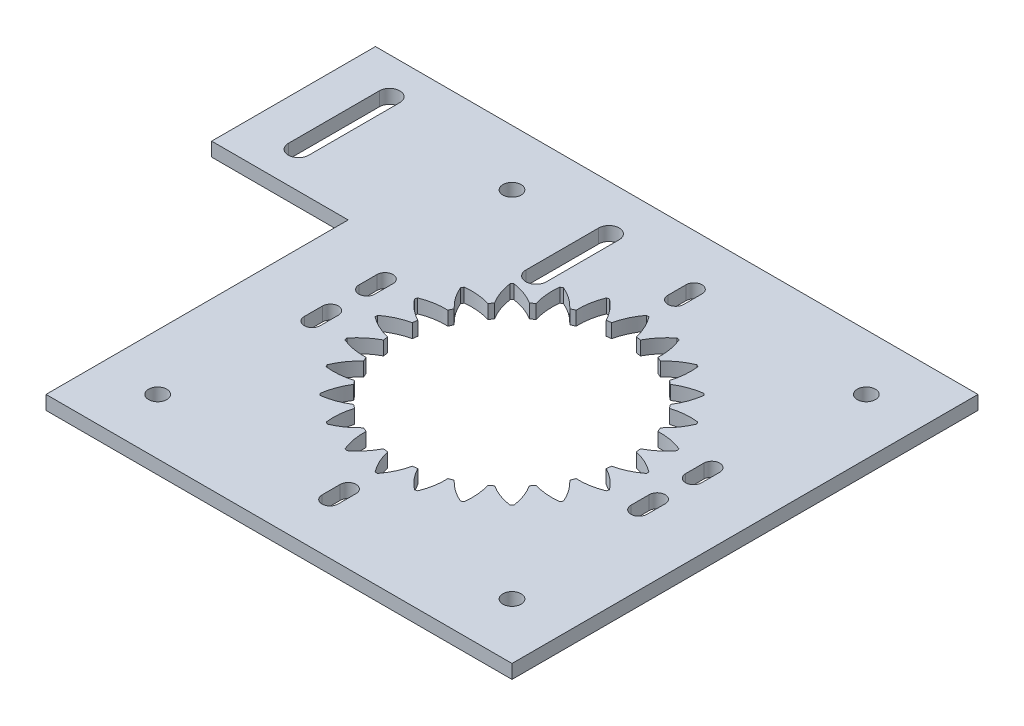
SolidWorks part; units mm, degrees
ref_plane "Front Plane" through (0, 0, 0) normal (0, 0, 1) x (1, 0, 0)
ref_plane "Top Plane" through (0, 0, 0) normal (0, 1, 0) x (1, 0, 0)
ref_plane "Right Plane" through (0, 0, 0) normal (1, 0, 0) x (0, 0, -1)
sketch "Sketch4" plane through (0, 0, 0) normal (0, 0, 1) x (1, 0, 0)
  line L0 (0, 0) -> (0, 40.0324) construction
sketch "Sketch1" plane through (0, 0, 0) normal (0, 1, 0) x (1, 0, 0)
  line L1 (-51.2, -51.2) -> (51.2, -51.2)
  line L2 (-51.2, -51.2) -> (-51.2, 15.2)
  line L3 (-51.2, 51.2) -> (51.2, 51.2)
  line L4 (51.2, -51.2) -> (51.2, 51.2)
  line L5 (-51.2, -51.2) -> (51.2, 51.2) construction
  line L6 (-51.2, 51.2) -> (51.2, -51.2) construction
  line L7 (-51.2, 51.2) -> (-81.2, 51.2)
  line L9 (-51.2, 15.2) -> (-81.2, 15.2)
  line L10 (-81.2, 51.2) -> (-81.2, 15.2)
  point P0 (0, 0)
  dimension "D1" = 102.4
  dimension "D2" = 102.4
  dimension "D3" = 30
  dimension "D4" = 36
extrude "Boss-Extrude1" add sketch "Sketch1" along normal blind 3.05
sketch "Sketch2" plane through (0, 3.05, 0) normal (0, 1, 0) x (1, 0, 0)
  arc B0 (7.4382, 28.8707) -> (3.7536, 24.4637) centre (15.7158, 18.2062) ccw
  arc B1 (7.9937, 28.7219) -> (7.4382, 28.8707) centre (0, 0) ccw
  arc B2 (8.9811, 23.063) -> (7.9937, 28.7219) centre (-4.5072, 23.6249) ccw
  arc B3 (9.9574, 22.6586) -> (8.9811, 23.063) centre (0, 0) ccw
  arc B4 (14.657, 25.9618) -> (9.9574, 22.6586) centre (19.8924, 13.5183) ccw
  arc B5 (15.1551, 25.6743) -> (14.657, 25.9618) centre (0, 0) ccw
  arc B6 (14.6443, 19.9527) -> (15.1551, 25.6743) centre (1.761, 23.9865) ccw
  arc B7 (15.4826, 19.3094) -> (14.6443, 19.9527) centre (0, 0) ccw
  arc B8 (20.877, 21.2837) -> (15.4826, 19.3094) centre (22.7134, 7.9092) ccw
  arc B9 (21.2837, 20.877) -> (20.877, 21.2837) centre (0, 0) ccw
  arc B10 (19.3094, 15.4826) -> (21.2837, 20.877) centre (7.9092, 22.7134) ccw
  arc B11 (19.9527, 14.6443) -> (19.3094, 15.4826) centre (0, 0) ccw
  arc B12 (25.6743, 15.1551) -> (19.9527, 14.6443) centre (23.9865, 1.761) ccw
  arc B13 (25.9618, 14.657) -> (25.6743, 15.1551) centre (0, 0) ccw
  arc B14 (22.6586, 9.9574) -> (25.9618, 14.657) centre (13.5183, 19.8924) ccw
  arc B15 (23.063, 8.9811) -> (22.6586, 9.9574) centre (0, 0) ccw
  arc B16 (28.7219, 7.9937) -> (23.063, 8.9811) centre (23.6249, -4.5072) ccw
  arc B17 (28.8707, 7.4382) -> (28.7219, 7.9937) centre (0, 0) ccw
  arc B18 (24.4637, 3.7536) -> (28.8707, 7.4382) centre (18.2062, 15.7158) ccw
  arc B19 (24.6016, 2.706) -> (24.4637, 3.7536) centre (0, 0) ccw
  arc B20 (29.8121, 0.2875) -> (24.6016, 2.706) centre (21.6534, -10.4682) ccw
  arc B21 (29.8121, -0.2875) -> (29.8121, 0.2875) centre (0, 0) ccw
  arc B22 (24.6016, -2.706) -> (29.8121, -0.2875) centre (21.6534, 10.4682) ccw
  arc B23 (24.4637, -3.7536) -> (24.6016, -2.706) centre (0, 0) ccw
  arc B24 (28.8707, -7.4382) -> (24.4637, -3.7536) centre (18.2062, -15.7158) ccw
  arc B25 (28.7219, -7.9937) -> (28.8707, -7.4382) centre (0, 0) ccw
  arc B26 (23.063, -8.9811) -> (28.7219, -7.9937) centre (23.6249, 4.5072) ccw
  arc B27 (22.6586, -9.9574) -> (23.063, -8.9811) centre (0, 0) ccw
  arc B28 (25.9618, -14.657) -> (22.6586, -9.9574) centre (13.5183, -19.8924) ccw
  arc B29 (25.6743, -15.1551) -> (25.9618, -14.657) centre (0, 0) ccw
  arc B30 (19.9527, -14.6443) -> (25.6743, -15.1551) centre (23.9865, -1.761) ccw
  arc B31 (19.3094, -15.4826) -> (19.9527, -14.6443) centre (0, 0) ccw
  arc B32 (21.2837, -20.877) -> (19.3094, -15.4826) centre (7.9092, -22.7134) ccw
  arc B33 (20.877, -21.2837) -> (21.2837, -20.877) centre (0, 0) ccw
  arc B34 (15.4826, -19.3094) -> (20.877, -21.2837) centre (22.7134, -7.9092) ccw
  arc B35 (14.6443, -19.9527) -> (15.4826, -19.3094) centre (0, 0) ccw
  arc B36 (15.1551, -25.6743) -> (14.6443, -19.9527) centre (1.761, -23.9865) ccw
  arc B37 (14.657, -25.9618) -> (15.1551, -25.6743) centre (0, 0) ccw
  arc B38 (9.9574, -22.6586) -> (14.657, -25.9618) centre (19.8924, -13.5183) ccw
  arc B39 (8.9811, -23.063) -> (9.9574, -22.6586) centre (0, 0) ccw
  arc B40 (7.9937, -28.7219) -> (8.9811, -23.063) centre (-4.5072, -23.6249) ccw
  arc B41 (7.4382, -28.8707) -> (7.9937, -28.7219) centre (0, 0) ccw
  arc B42 (3.7536, -24.4637) -> (7.4382, -28.8707) centre (15.7158, -18.2062) ccw
  arc B43 (2.706, -24.6016) -> (3.7536, -24.4637) centre (0, 0) ccw
  arc B44 (0.2875, -29.8121) -> (2.706, -24.6016) centre (-10.4682, -21.6534) ccw
  arc B45 (-0.2875, -29.8121) -> (0.2875, -29.8121) centre (0, 0) ccw
  arc B46 (-2.706, -24.6016) -> (-0.2875, -29.8121) centre (10.4682, -21.6534) ccw
  arc B47 (-3.7536, -24.4637) -> (-2.706, -24.6016) centre (0, 0) ccw
  arc B48 (-7.4382, -28.8707) -> (-3.7536, -24.4637) centre (-15.7158, -18.2062) ccw
  arc B49 (-7.9937, -28.7219) -> (-7.4382, -28.8707) centre (0, 0) ccw
  arc B50 (-8.9811, -23.063) -> (-7.9937, -28.7219) centre (4.5072, -23.6249) ccw
  arc B51 (-9.9574, -22.6586) -> (-8.9811, -23.063) centre (0, 0) ccw
  arc B52 (-14.657, -25.9618) -> (-9.9574, -22.6586) centre (-19.8924, -13.5183) ccw
  arc B53 (-15.1551, -25.6743) -> (-14.657, -25.9618) centre (0, 0) ccw
  arc B54 (-14.6443, -19.9527) -> (-15.1551, -25.6743) centre (-1.761, -23.9865) ccw
  arc B55 (-15.4826, -19.3094) -> (-14.6443, -19.9527) centre (0, 0) ccw
  arc B56 (-20.877, -21.2837) -> (-15.4826, -19.3094) centre (-22.7134, -7.9092) ccw
  arc B57 (-21.2837, -20.877) -> (-20.877, -21.2837) centre (0, 0) ccw
  arc B58 (-19.3094, -15.4826) -> (-21.2837, -20.877) centre (-7.9092, -22.7134) ccw
  arc B59 (-19.9527, -14.6443) -> (-19.3094, -15.4826) centre (0, 0) ccw
  arc B60 (-25.6743, -15.1551) -> (-19.9527, -14.6443) centre (-23.9865, -1.761) ccw
  arc B61 (-25.9618, -14.657) -> (-25.6743, -15.1551) centre (0, 0) ccw
  arc B62 (-22.6586, -9.9574) -> (-25.9618, -14.657) centre (-13.5183, -19.8924) ccw
  arc B63 (-23.063, -8.9811) -> (-22.6586, -9.9574) centre (0, 0) ccw
  arc B64 (-28.7219, -7.9937) -> (-23.063, -8.9811) centre (-23.6249, 4.5072) ccw
  arc B65 (-28.8707, -7.4382) -> (-28.7219, -7.9937) centre (0, 0) ccw
  arc B66 (-24.4637, -3.7536) -> (-28.8707, -7.4382) centre (-18.2062, -15.7158) ccw
  arc B67 (-24.6016, -2.706) -> (-24.4637, -3.7536) centre (0, 0) ccw
  arc B68 (-29.8121, -0.2875) -> (-24.6016, -2.706) centre (-21.6534, 10.4682) ccw
  arc B69 (-29.8121, 0.2875) -> (-29.8121, -0.2875) centre (0, 0) ccw
  arc B70 (-24.6016, 2.706) -> (-29.8121, 0.2875) centre (-21.6534, -10.4682) ccw
  arc B71 (-24.4637, 3.7536) -> (-24.6016, 2.706) centre (0, 0) ccw
  arc B72 (-28.8707, 7.4382) -> (-24.4637, 3.7536) centre (-18.2062, 15.7158) ccw
  arc B73 (-28.7219, 7.9937) -> (-28.8707, 7.4382) centre (0, 0) ccw
  arc B74 (-23.063, 8.9811) -> (-28.7219, 7.9937) centre (-23.6249, -4.5072) ccw
  arc B75 (-22.6586, 9.9574) -> (-23.063, 8.9811) centre (0, 0) ccw
  arc B76 (-25.9618, 14.657) -> (-22.6586, 9.9574) centre (-13.5183, 19.8924) ccw
  arc B77 (-25.6743, 15.1551) -> (-25.9618, 14.657) centre (0, 0) ccw
  arc B78 (-19.9527, 14.6443) -> (-25.6743, 15.1551) centre (-23.9865, 1.761) ccw
  arc B79 (-19.3094, 15.4826) -> (-19.9527, 14.6443) centre (0, 0) ccw
  arc B80 (-21.2837, 20.877) -> (-19.3094, 15.4826) centre (-7.9092, 22.7134) ccw
  arc B81 (-20.877, 21.2837) -> (-21.2837, 20.877) centre (0, 0) ccw
  arc B82 (-15.4826, 19.3094) -> (-20.877, 21.2837) centre (-22.7134, 7.9092) ccw
  arc B83 (-14.6443, 19.9527) -> (-15.4826, 19.3094) centre (0, 0) ccw
  arc B84 (-15.1551, 25.6743) -> (-14.6443, 19.9527) centre (-1.761, 23.9865) ccw
  arc B85 (-14.657, 25.9618) -> (-15.1551, 25.6743) centre (0, 0) ccw
  arc B86 (-9.9574, 22.6586) -> (-14.657, 25.9618) centre (-19.8924, 13.5183) ccw
  arc B87 (-8.9811, 23.063) -> (-9.9574, 22.6586) centre (0, 0) ccw
  arc B88 (-7.9937, 28.7219) -> (-8.9811, 23.063) centre (4.5072, 23.6249) ccw
  arc B89 (-7.4382, 28.8707) -> (-7.9937, 28.7219) centre (0, 0) ccw
  arc B90 (-3.7536, 24.4637) -> (-7.4382, 28.8707) centre (-15.7158, 18.2062) ccw
  arc B91 (-2.706, 24.6016) -> (-3.7536, 24.4637) centre (0, 0) ccw
  arc B92 (-0.2875, 29.8121) -> (-2.706, 24.6016) centre (10.4682, 21.6534) ccw
  arc B93 (0.2875, 29.8121) -> (-0.2875, 29.8121) centre (0, 0) ccw
  arc B94 (2.706, 24.6016) -> (0.2875, 29.8121) centre (-10.4682, 21.6534) ccw
  arc B95 (3.7536, 24.4637) -> (2.706, 24.6016) centre (0, 0) ccw
sketch_block_instance "Block1-1"
sketch_block "Block1"
extrude "Cut-Extrude1" cut sketch "Sketch2" against normal blind 10
sketch "Sketch3" plane through (0, 3.05, 0) normal (0, 1, 0) x (1, 0, 0)
  line L0 (51.2, -51.2) -> (51.2, 51.2) construction
  line L1 (51.2, 51.2) -> (-81.2, 51.2) construction
  circle A0 centre (38.93, 38.93) radius 2
  dimension "D3" = 4
  dimension "D1" = 12.27
  dimension "D2" = 12.27
extrude "Cut-Extrude2" cut sketch "Sketch3" against normal blind 10
pattern_circular "CirPattern1" count 4 over 360 about axis through (0, 0, 0) along (0, 1, 0) of "Cut-Extrude2"
sketch "Sketch7" plane through (0, 3.05, 0) normal (0, 1, 0) x (1, 0, 0)
  line L0 (-49.6947, 0) -> (47.5674, 0) construction
  line L1 (0, -37.2684) -> (0, -38.7316) construction
  line L2 (1.75, -37.2684) -> (1.75, -38.7316)
  line L3 (-1.75, -37.2684) -> (-1.75, -38.7316)
  line L4 (0, -40) -> (0, -36) construction
  line L5 (-1.75, -40) -> (-1.75, -36)
  line L6 (1.75, -40) -> (1.75, -36)
  arc A0 (1.75, -37.2684) -> (-1.75, -37.2684) centre (0, -37.2684) ccw
  arc A1 (-1.75, -38.7316) -> (1.75, -38.7316) centre (0, -38.7316) ccw
  arc A2 (-1.75, -40) -> (1.75, -40) centre (0, -40) ccw
  arc A3 (1.75, -36) -> (-1.75, -36) centre (0, -36) ccw
  point P5 (0, -38)
  point P12 (0, -38)
  dimension "D1" = 38
  dimension "D2" = 3.5
  dimension "D3" = 4
extrude "Cut-Extrude3" cut sketch "Sketch7" against normal up to surface (3.05 mm away) contours A3 L5 A2 L6 up to face at (38.93, 0, 36.93)
sketch "Sketch9" plane through (0, 3.05, 0) normal (0, 1, 0) x (1, 0, 0)
  line L0 (-54.2517, 0) -> (57.2543, 0) construction
  line L1 (35.9, -4) -> (35.9, -8) construction
  line L2 (37.65, -4) -> (37.65, -8)
  line L3 (34.15, -4) -> (34.15, -8)
  line L4 (51.2, -51.2) -> (51.2, 51.2) construction
  arc A0 (37.65, -4) -> (34.15, -4) centre (35.9, -4) ccw
  arc A1 (34.15, -8) -> (37.65, -8) centre (35.9, -8) ccw
  point P5 (35.9, -6)
  dimension "D3" = 15.3
  dimension "D1" = 3.5
  dimension "D2" = 4
  dimension "D4" = 6
extrude "Cut-Extrude4" cut sketch "Sketch9" against normal blind 10
mirror "Mirror1" about plane through (0, 0, 0) normal (1, 0, 0) of "Cut-Extrude4"
mirror "Mirror2" about plane through (0, 0, 0) normal (0, 0, 1) of "Cut-Extrude3", "Mirror1"
sketch "Sketch10" plane through (0, 3.05, 0) normal (0, 1, 0) x (1, 0, 0)
  line L0 (-70.1, 43.2) -> (-70.1, 23.2) construction
  line L1 (-67.85, 43.2) -> (-67.85, 23.2)
  line L2 (-72.35, 43.2) -> (-72.35, 23.2)
  line L3 (51.2, 51.2) -> (-81.2, 51.2) construction
  line L4 (-19.9, 25.2) -> (-19.9, 41.2) construction
  line L5 (-22.15, 25.2) -> (-22.15, 41.2)
  line L6 (-17.65, 25.2) -> (-17.65, 41.2)
  arc A0 (-67.85, 43.2) -> (-72.35, 43.2) centre (-70.1, 43.2) ccw
  arc A1 (-72.35, 23.2) -> (-67.85, 23.2) centre (-70.1, 23.2) ccw
  arc A2 (-22.15, 25.2) -> (-17.65, 25.2) centre (-19.9, 25.2) ccw
  arc A3 (-17.65, 41.2) -> (-22.15, 41.2) centre (-19.9, 41.2) ccw
  point P2 (-70.1, 33.2)
  point P12 (-19.9, 33.2)
  dimension "D1" = 4.5
  dimension "D2" = 20
  dimension "D3" = 70.1
  dimension "D4" = 18
  dimension "D5" = 4.5
  dimension "D6" = 16
  dimension "D7" = 50.2
extrude "Cut-Extrude5" cut sketch "Sketch10" against normal blind 10
